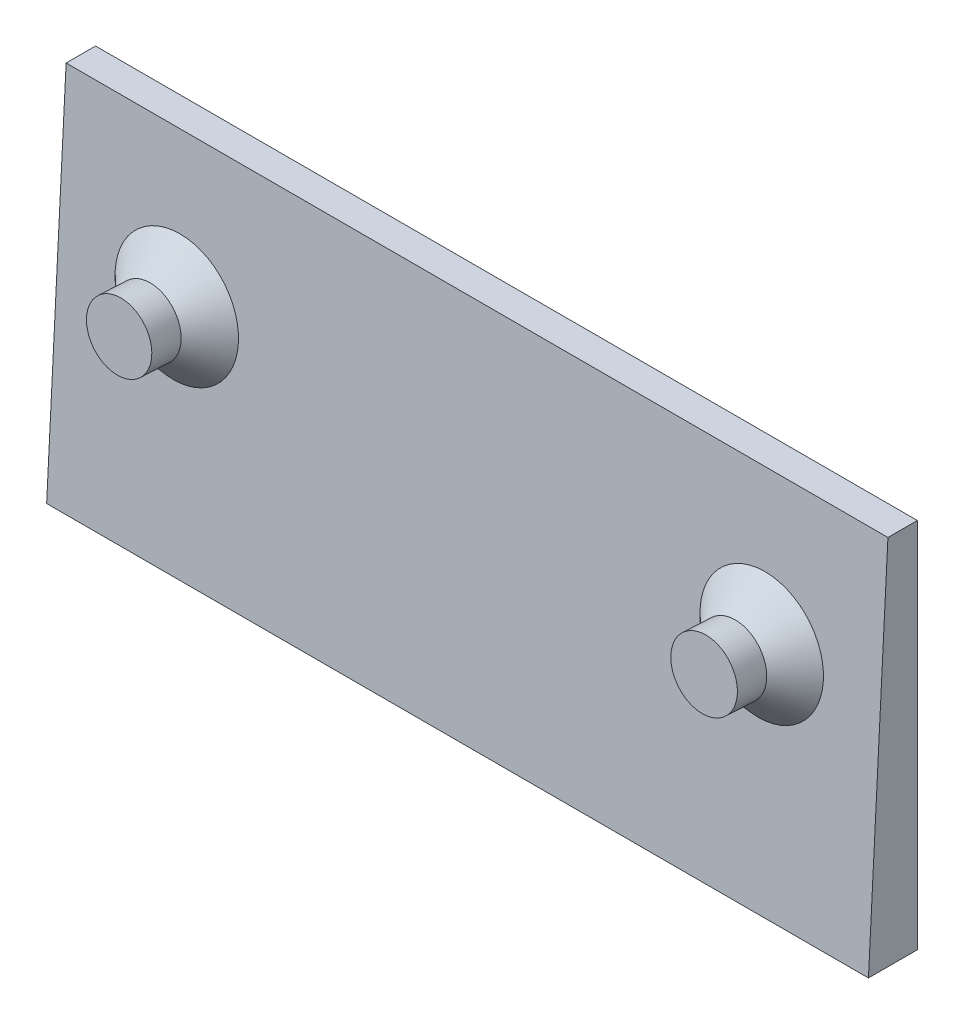
SolidWorks part; units mm, degrees
ref_plane "Top Plane" through (0, 0, 0) normal (0, 0, 1) x (1, 0, 0)
ref_plane "Front Plane" through (0, 0, 0) normal (0, 1, 0) x (1, 0, 0)
ref_plane "Right Plane" through (0, 0, 0) normal (1, 0, 0) x (0, 0, -1)
sketch "Sketch1" plane through (0, 0, 0) normal (0, 0, 1) x (1, 0, 0)
  line L1 (-42, -19) -> (42, -19)
  line L2 (-42, -19) -> (-42, 19)
  line L3 (-42, 19) -> (42, 19)
  line L4 (42, -19) -> (42, 19)
  line L5 (-42, -19) -> (42, 19) construction
  line L6 (-42, 19) -> (42, -19) construction
  point P0 (0, 0)
  dimension "D1" = 84
  dimension "D2" = 38
extrude "Boss-Extrude1" add sketch "Sketch1" along normal blind 5
sketch "Sketch2" plane through (0, 0, 5) normal (0, 0, 1) x (1, 0, 0)
  line L1 (-42, -19) -> (42, -19)
  line L2 (-42, -19) -> (-42, 22.1553)
  line L3 (-42, 22.1553) -> (42, 22.1553)
  line L4 (42, -19) -> (42, 22.1553)
revolve "Cut-Revolve1" cut sketch "Sketch2" angle 3 about L1 reverse direction yes
sketch "Sketch3" plane through (0, 0.2093, 3.9933) normal (0, 0.0523, 0.9986) x (1, 0, 0)
  line L0 (-29.8957, 3.6644) -> (29.8957, 3.6644) construction
  circle A0 centre (-29.8957, 3.6644) radius 6.3
  circle A1 centre (29.8957, 3.6644) radius 6.3
ref_plane "Plane1" through (0, 0.314, 5.9905) normal (0, 0.0523, 0.9986) x (1, 0, 0)
ref_plane "Plane2" through (0, 0.3611, 6.8893) normal (0, -0.0523, -0.9986) x (-1, 0, 0)
sketch "Sketch5" plane through (0, 0.3611, 6.8893) normal (0, -0.0523, -0.9986) x (-1, 0, 0)
  line L0 (29.8957, 3.6644) -> (-29.8957, 3.6644) construction
  circle A2 centre (29.8957, 3.6644) radius 3.3352
  circle A3 centre (-29.8957, 3.6644) radius 3.4
loft "Loft2" add section "Sketch3" section "Sketch5" connector at (-23.5957, 3.8692, 3.8015) connector at (-26.5605, 4.0204, 6.6975)
loft "Loft3" add section "Sketch3<4>" section "Sketch5<4>" connector at (23.5957, 3.8693, 3.8015) connector at (26.4957, 4.0214, 6.6975)
sketch "Sketch3<4>" plane through (0, 0.2093, 3.9933) normal (0, 0.0523, 0.9986) x (1, 0, 0) same geometry as "Sketch3"
sketch "Sketch5<4>" plane through (0, 0.3611, 6.8893) normal (0, -0.0523, -0.9986) x (-1, 0, 0) same geometry as "Sketch5"
extrude "Boss-Extrude2" add sketch "Sketch5<8>" against normal blind 3
sketch "Sketch5<8>" plane through (0, 0.3611, 6.8893) normal (0, -0.0523, -0.9986) x (-1, 0, 0) same geometry as "Sketch5"
